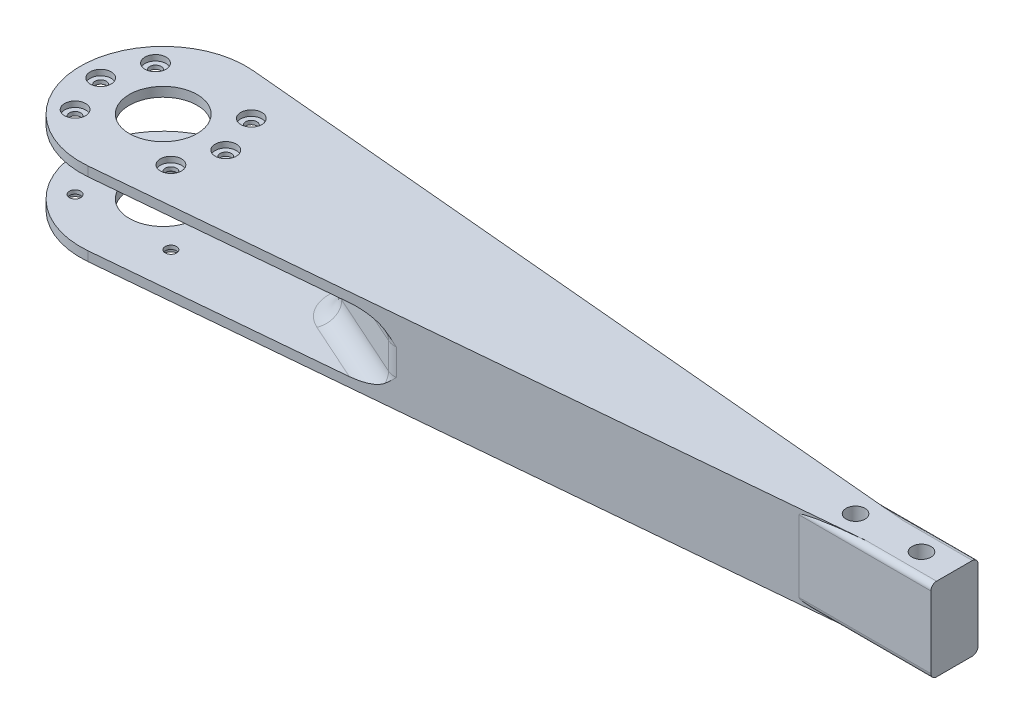
SolidWorks part; units mm, degrees
ref_plane "Front Plane" through (0, 0, 0) normal (0, 0, 1) x (1, 0, 0)
ref_plane "Top Plane" through (0, 0, 0) normal (0, 1, 0) x (1, 0, 0)
ref_plane "Right Plane" through (0, 0, 0) normal (1, 0, 0) x (0, 0, -1)
sketch "Sketch1" plane through (0, 0, 0) normal (0, 1, 0) x (1, 0, 0)
  line L0 (12.7163, 10.6703) -> (0, 0) construction
  line L1 (0, 21.6534) -> (0, -27.8122) construction
  line L2 (-17.8639, 0) -> (22.5422, 0) construction
  line L3 (0, 0) -> (210, 0) construction
  line L4 (175, 6.25) -> (1.9832, 21.9104)
  line L5 (175, 6.25) -> (210, 6.25)
  line L6 (175, 6.25) -> (175, -6.25) construction
  line L7 (175, -6.25) -> (210, -6.25)
  line L8 (210, 6.25) -> (210, -6.25)
  line L9 (175, 6.25) -> (210, -6.25) construction
  line L10 (175, -6.25) -> (210, 6.25) construction
  line L11 (175, -6.25) -> (1.9832, -21.9104)
  line L12 (192.5, 0) -> (175, 0) construction
  line L13 (192.5, 0) -> (210, 0) construction
  line L14 (41.8131, 0) -> (75.7048, 15.2376)
  line L15 (41.8131, 0) -> (75.7048, -15.2376)
  circle A0 centre (0, 0) radius 16.6 construction
  circle A1 centre (16.6, 0) radius 1.5
  circle A2 centre (12.7163, 10.6703) radius 1.5
  circle A3 centre (12.7163, -10.6703) radius 1.5
  circle A4 centre (-12.7163, 10.6703) radius 1.5
  circle A5 centre (-12.7163, -10.6703) radius 1.5
  circle A6 centre (-16.6, 0) radius 1.5
  circle A7 centre (0, 0) radius 9
  circle A8 centre (0, 0) radius 22
  circle A9 centre (183.75, 0) radius 2.5
  circle A10 centre (201.25, 0) radius 2.5
  circle A11 centre (0, 0) radius 26
  point P21 (192.5, 0)
  dimension "D1" = 33.2
  dimension "D2" = 3
  dimension "D3" = 3
  dimension "D5" = 18
  dimension "D6" = 44
  dimension "D8" = 12.5
  dimension "D10" = 5
  dimension "D11" = 5
  dimension "D12" = 52
  dimension "D4" = 40
  dimension "D7" = 210
  dimension "D9" = 35
extrude "Boss-Extrude1" add sketch "Sketch1" along normal blind 22 contours A8 L11 L7 L8 L5 L4 A10 A9 region at (118.9546, 0, 0)
extrude "Boss-Extrude2" add sketch "Sketch1<3>" along normal blind 2.5 contours A8 A6 A5 A3 A2 A1 A4 A7 | L11 A11 L4 A8 | A11 L11 L15 L14 L4 region at (41.8035, 0, 0) region at (22.8583, 0, -11.3032) region at (15.783, 0, -14.4189)
sketch "Sketch1<3>" plane through (0, 0, 0) normal (0, 1, 0) x (1, 0, 0) same geometry as "Sketch1"
extrude "Boss-Extrude3" add sketch "Sketch1<4>" against normal blind 2.5 from surface contours A8 A6 A5 A3 A2 A1 A4 A7 | L11 A11 L4 A8 | A11 L11 L15 L14 L4 region at (41.8035, 0, 0) region at (22.8583, 0, -11.3032) region at (15.783, 0, -14.4189) starting at face at (201.25, 22, 2.5)
sketch "Sketch1<4>" plane through (0, 0, 0) normal (0, 1, 0) x (1, 0, 0) same geometry as "Sketch1"
fillet "Fillet1" radius 5 3 edges at (75.7048, 11, 15.2376) (75.7048, 11, -15.2376) (41.8131, 11, 0)
fillet "Fillet2" radius 5 10 edges at (75.7328, 2.5, -15.071) (63.2327, 2.5, -9.6302) (49.0065, 2.5, 0) (75.7328, 2.5, 15.071) (75.7328, 19.5, 15.071) (75.7328, 19.5, -15.071) (63.2327, 19.5, -9.6302) (49.0065, 19.5, 0) (63.2327, 2.5, 9.6302) (63.2327, 19.5, 9.6302)
sketch "Sketch2" plane through (0, 0, 0) normal (0, -1, 0) x (1, 0, 0)
  line L0 (0, 0) -> (12.7163, 10.6703) construction
  line L1 (0, 0) -> (16.6, 0) construction
  line L2 (0, 0) -> (-12.7163, 10.6703) construction
  line L3 (0, 0) -> (-16.6, 0) construction
  circle A0 centre (0, 0) radius 16.6 construction
  circle A1 centre (-12.7163, 10.6703) radius 1.5 construction
  circle A2 centre (-16.6, 0) radius 1.5 construction
  circle A3 centre (-12.7163, -10.6703) radius 1.5 construction
  circle A4 centre (12.7163, -10.6703) radius 1.5 construction
  circle A5 centre (16.6, 0) radius 1.5 construction
  circle A6 centre (12.7163, 10.6703) radius 1.5 construction
  circle A7 centre (-12.7163, 10.6703) radius 1.5 construction
  circle A8 centre (-16.6, 0) radius 1.5 construction
  circle A9 centre (-12.7163, -10.6703) radius 1.5 construction
  circle A10 centre (12.7163, -10.6703) radius 1.5 construction
  circle A11 centre (16.6, 0) radius 1.5 construction
  circle A12 centre (12.7163, 10.6703) radius 1.5 construction
  circle A13 centre (12.7163, 10.6703) radius 2.8
  circle A14 centre (16.6, 0) radius 2.8
  circle A15 centre (12.7163, -10.6703) radius 2.8
  circle A16 centre (-12.7163, 10.6703) radius 2.8
  circle A17 centre (-16.6, 0) radius 2.8
  circle A18 centre (-12.7163, -10.6703) radius 2.8
  dimension "D1" = 33.2
  dimension "D2" = 5.6
  dimension "D5" = 5.6
  dimension "D4" = 40
  dimension "D7" = 40
  dimension "D3" = 3
  dimension "D6" = 3
extrude "Cut-Extrude3" cut sketch "Sketch2" against normal blind 1.5
extrude "Cut-Extrude4" cut sketch "Sketch2<3>" along normal blind 1.5 from surface starting at face at (124.9972, 22, 0)
sketch "Sketch2<3>" plane through (0, 0, 0) normal (0, -1, 0) x (1, 0, 0) same geometry as "Sketch2"
fillet "Fillet3" radius 1.5 4 edges at (192.5, 0, 6.25) (192.5, 0, -6.25) (192.5, 22, -6.25) (192.5, 22, 6.25) tangent propagation no
